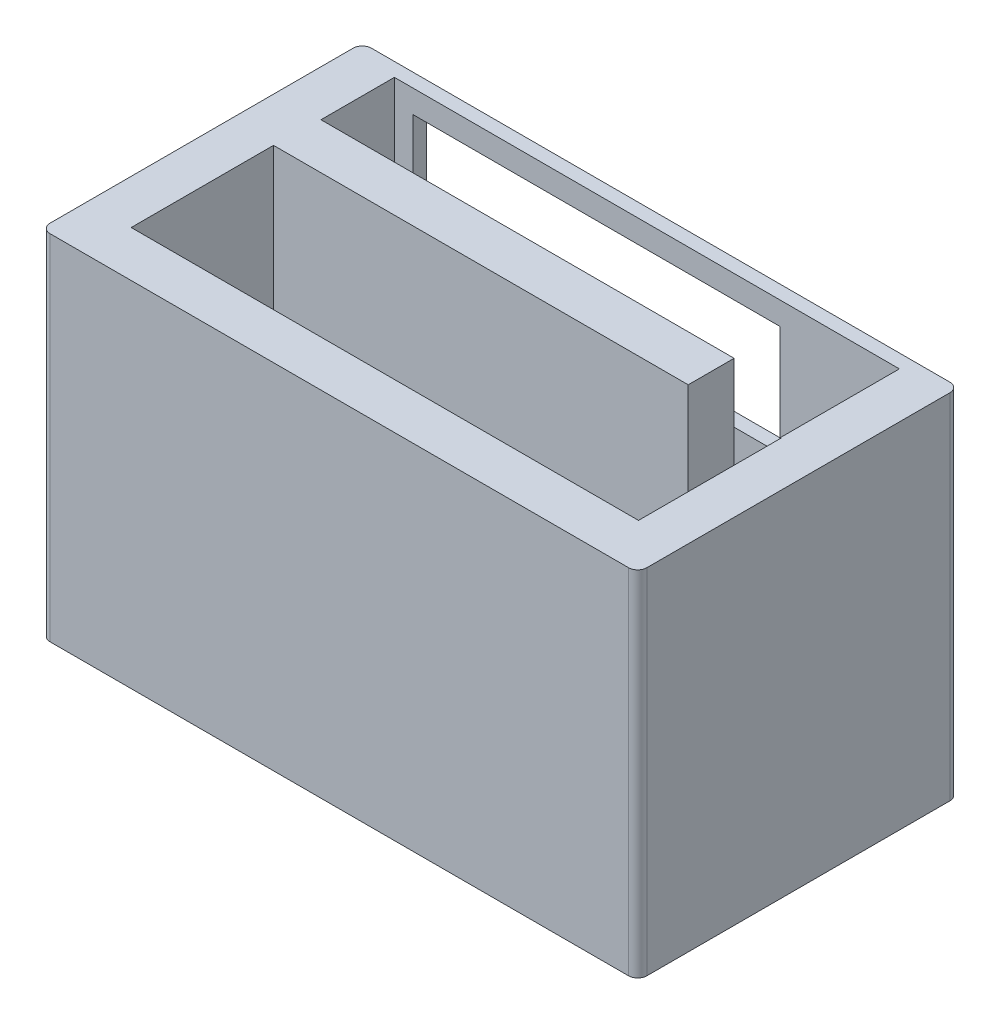
SolidWorks part; units mm, degrees
ref_plane "Plan de face" through (0, 0, 0) normal (0, 0, 1) x (1, 0, 0)
ref_plane "Plan de dessus" through (0, 0, 0) normal (0, 1, 0) x (1, 0, 0)
ref_plane "Plan de droite" through (0, 0, 0) normal (1, 0, 0) x (0, 0, -1)
sketch "Esquisse1" plane through (0, 0, 0) normal (0, 1, 0) x (1, 0, 0)
  line L1 (-65, 35) -> (65, 35)
  line L2 (-65, 35) -> (-65, -35)
  line L3 (-65, -35) -> (65, -35)
  line L4 (65, 35) -> (65, -35)
  point P4 (0, -35)
  dimension "D1" = 65
  dimension "D2" = 130
  dimension "D3" = 70
  dimension "D4" = 35
extrude "Boss.-Extru.1" add sketch "Esquisse1" along normal blind 77
sketch "Esquisse4" plane through (0, 77, 0) normal (0, 1, 0) x (1, 0, 0)
  line L0 (65, -35) -> (65, 35) construction
  line L1 (55, 16) -> (-55, 16)
  line L2 (55, 16) -> (55, 32)
  line L3 (55, 32) -> (-55, 32)
  line L4 (-55, 16) -> (-55, 32)
  line L5 (65, 35) -> (-65, 35) construction
  line L6 (-65, 35) -> (-65, -35) construction
  dimension "D1" = 10
  dimension "D2" = 3
  dimension "D3" = 10
  dimension "D4" = 16
extrude "Enlèv. mat.-Extru.1" cut sketch "Esquisse4" against normal blind 72
sketch "Esquisse7" plane through (0, 0, -35) normal (0, 0, -1) x (-1, 0, 0)
  line L0 (65, 77) -> (65, 0) construction
  line L1 (-29, 35) -> (51, 35)
  line L2 (-29, 35) -> (-29, 11)
  line L3 (-29, 11) -> (51, 11)
  line L4 (51, 35) -> (51, 11)
  line L5 (-65, 0) -> (65, 0) construction
  dimension "D1" = 14
  dimension "D2" = 11
  dimension "D3" = 80
  dimension "D4" = 24
extrude "Enlèv. mat.-Extru.2" cut sketch "Esquisse7" against normal blind 5
sketch "Esquisse8" plane through (0, 0, -35) normal (0, 0, -1) x (-1, 0, 0)
  line L0 (51, 35) -> (-29, 35) construction
  line L1 (-29, 72) -> (51, 72)
  line L2 (-29, 72) -> (-29, 48)
  line L3 (-29, 48) -> (51, 48)
  line L4 (51, 72) -> (51, 48)
  line L7 (65, 77) -> (65, 0) construction
  dimension "D1" = 13
  dimension "D2" = 24
  dimension "D3" = 80
  dimension "D4" = 14
extrude "Enlèv. mat.-Extru.3" cut sketch "Esquisse8" against normal blind 5
fillet "Congé1" radius 2 4 edges at (65, 38.5, 35) (-65, 38.5, 35) (-65, 38.5, -35) (65, 38.5, -35)
sketch "Esquisse9" plane through (0, 77, 0) normal (0, 1, 0) x (1, 0, 0)
  line L0 (-63, -35) -> (63, -35) construction
  line L1 (-55.3379, -25) -> (55.1719, -25)
  line L2 (-55.3379, -25) -> (-55.3379, 6)
  line L3 (-55.3379, 6) -> (55.1719, 6)
  line L4 (55.1719, -25) -> (55.1719, 6)
  line L5 (-55, 16) -> (55, 16) construction
  dimension "D1" = 10
  dimension "D2" = 10
extrude "Enlèv. mat.-Extru.4" cut sketch "Esquisse9" against normal blind 72
sketch "Esquisse10" plane through (0, 77, 0) normal (0, 1, 0) x (1, 0, 0)
  line L0 (55, 16) -> (55, 32) construction
  line L1 (35, 3.7616) -> (55, 3.7616)
  line L2 (35, 3.7616) -> (35, 19.1008)
  line L3 (35, 19.1008) -> (55, 19.1008)
  line L4 (55, 3.7616) -> (55, 19.1008)
  dimension "D1" = 0
  dimension "D2" = 20
extrude "Enlèv. mat.-Extru.5" cut sketch "Esquisse10" against normal blind 72
